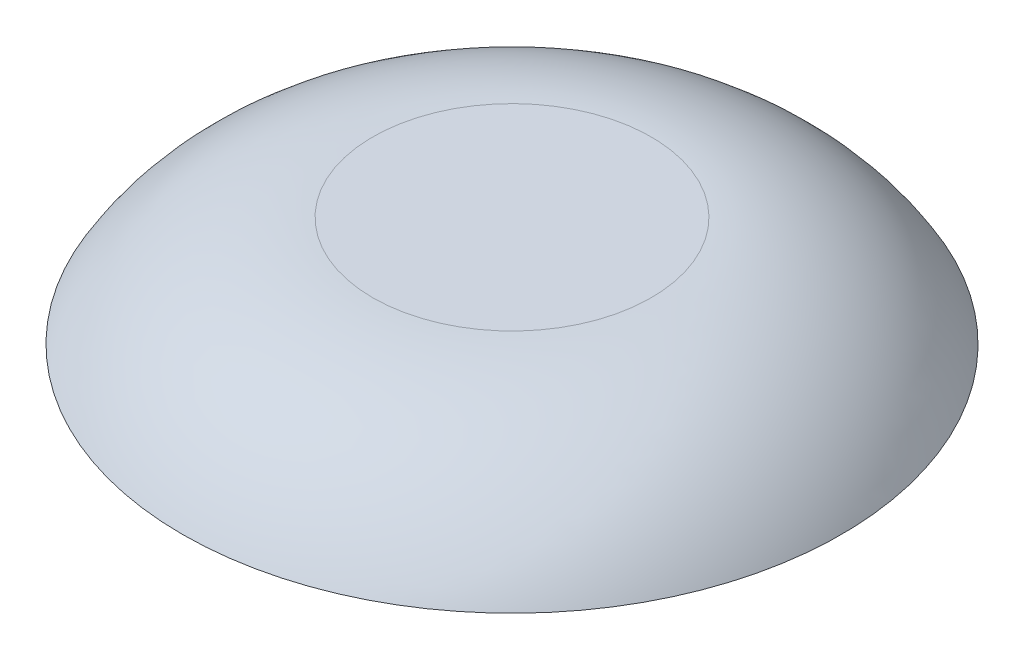
SolidWorks part; units mm, degrees
ref_plane "Спереди" through (0, 0, 0) normal (0, 0, 1) x (1, 0, 0)
ref_plane "Сверху" through (0, 0, 0) normal (0, 1, 0) x (1, 0, 0)
ref_plane "Справа" through (0, 0, 0) normal (1, 0, 0) x (0, 0, -1)
sketch "Sketch1" plane through (0, 0, 0) normal (0, 1, 0) x (1, 0, 0)
  circle A0 centre (0, 0) radius 15
  dimension "D1" = 30
extrude "Boss-Extrude1" add sketch "Sketch1" along normal blind 5
fillet "Fillet1" radius 10 1 edges at (0, 5, 15)
